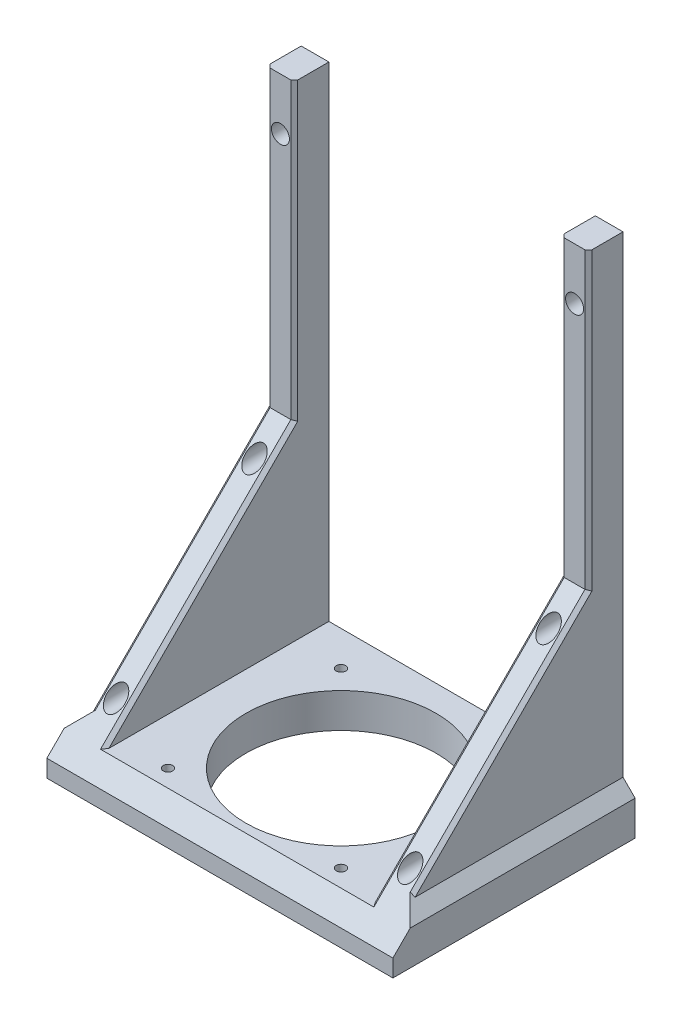
SolidWorks part; units mm, degrees
ref_plane "Front Plane" through (0, 0, 0) normal (0, 0, 1) x (1, 0, 0)
ref_plane "Top Plane" through (0, 0, 0) normal (0, 1, 0) x (1, 0, 0)
ref_plane "Right Plane" through (0, 0, 0) normal (1, 0, 0) x (0, 0, -1)
sketch "Sketch1" plane through (0, 0, 0) normal (0, 1, 0) x (1, 0, 0)
  line L1 (-70.1268, 59.4014) -> (29.8732, 59.4014)
  line L2 (-70.1268, 59.4014) -> (-70.1268, -10.5986)
  line L3 (-70.1268, -10.5986) -> (29.8732, -10.5986)
  line L4 (29.8732, 59.4014) -> (29.8732, -10.5986)
  line L5 (-70.1268, 59.4014) -> (29.8732, -10.5986) construction
  line L6 (-70.1268, -10.5986) -> (29.8732, 59.4014) construction
  line L15 (-40.8213, 9.9152) -> (14.7135, 48.7896) construction
  line L16 (-42.0419, 46.3165) -> (1.7884, 2.4863) construction
  line L17 (-45.1268, -0.5986) -> (4.8732, -0.5986)
  line L18 (-45.1268, -0.5986) -> (-45.1268, 49.4014)
  line L19 (-45.1268, 49.4014) -> (4.8732, 49.4014)
  line L20 (4.8732, -0.5986) -> (4.8732, 49.4014)
  line L21 (-45.1268, -0.5986) -> (4.8732, 49.4014) construction
  line L22 (-45.1268, 49.4014) -> (4.8732, -0.5986) construction
  circle A2 centre (-45.1268, 49.4014) radius 1.375
  circle A3 centre (4.8732, 49.4014) radius 1.375
  circle A4 centre (4.8732, -0.5986) radius 1.375
  circle A5 centre (-45.1268, -0.5986) radius 1.375
  circle A6 centre (-20.1268, 24.4014) radius 27.5
  point P0 (-20.1268, 24.4014)
  point P5 (-20.1268, 24.4014)
  point P8 (-20.1268, 24.4014)
  point P12 (-20.1268, 24.4014)
  dimension "D2" = 50
  dimension "D4" = 50
  dimension "D1" = 70
  dimension "D3" = 100
extrude "Boss-Extrude1" add sketch "Sketch1" against normal blind 10 contours L2 L3 L4 L1 | A2 | A3 | A6 | A4 | A5
sketch "Sketch3" plane through (0, 0, 0) normal (0, 1, 0) x (1, 0, 0)
  line L0 (-70.1268, 59.4014) -> (29.8732, 59.4014) construction
  line L1 (-55.1268, -10.5986) -> (14.8732, -10.5986)
  line L2 (-55.1268, -10.5986) -> (-55.1268, 59.4014)
  line L3 (-55.1268, 59.4014) -> (14.8732, 59.4014)
  line L4 (14.8732, -10.5986) -> (14.8732, 59.4014)
  line L5 (-55.1268, -10.5986) -> (14.8732, 59.4014) construction
  line L6 (-55.1268, 59.4014) -> (14.8732, -10.5986) construction
  line L7 (-70.1268, 59.4014) -> (-55.1268, 59.4014) construction
  line L8 (-20.1268, 59.4014) -> (-20.1268, -10.5986)
  line L9 (-66.6268, -10.5986) -> (-58.6268, -10.5986)
  line L10 (-66.6268, -10.5986) -> (-66.6268, 59.4014)
  line L11 (-66.6268, 59.4014) -> (-58.6268, 59.4014)
  line L12 (-58.6268, -10.5986) -> (-58.6268, 59.4014)
  line L13 (-66.6268, -10.5986) -> (-58.6268, 59.4014) construction
  line L14 (-66.6268, 59.4014) -> (-58.6268, -10.5986) construction
  line L15 (26.3732, 59.4014) -> (18.3732, 59.4014)
  line L16 (18.3732, -10.5986) -> (18.3732, 59.4014)
  line L17 (26.3732, -10.5986) -> (18.3732, -10.5986)
  line L18 (26.3732, -10.5986) -> (26.3732, 59.4014)
  point P0 (-20.1268, 24.4014)
  point P9 (-62.6268, 24.4014)
  line M15 (29.8732, 59.4014) -> (-70.1268, 59.4014)
  line M17 (-70.1268, -10.5986) -> (29.8732, -10.5986)
  dimension "D1" = 70
  dimension "D2" = 8
extrude "Boss-Extrude2" add sketch "Sketch3" along normal blind 55 contours L12 L10 M17 M15 | L18 L16 M17 M15 region at (-62.6268, 0, -24.4014) region at (22.3732, 0, -24.4014)
chamfer "Chamfer1" distance 60 angle 45 1 edges at (-62.6268, 55, 10.5986)
chamfer "Chamfer2" distance 3.5 angle 45 2 edges at (26.3732, 0, -26.9014) (-66.6268, 0, -26.9014)
sketch "Sketch5" plane through (0, 55, 0) normal (0, 1, 0) x (1, 0, 0)
  line L0 (18.3732, -5.5986) -> (18.3732, 59.4014) construction
  line L1 (-66.6268, 59.4014) -> (-58.6268, 59.4014)
  line L2 (-66.6268, 59.4014) -> (-66.6268, 49.4014)
  line L3 (-66.6268, 49.4014) -> (-58.6268, 49.4014)
  line L4 (-58.6268, 59.4014) -> (-58.6268, 49.4014)
  line L5 (26.3732, 59.4014) -> (18.3732, 59.4014)
  line L6 (26.3732, 59.4014) -> (26.3732, 49.4014)
  line L7 (26.3732, 49.4014) -> (18.3732, 49.4014)
  line L8 (18.3732, 59.4014) -> (18.3732, 49.4014)
  line L9 (18.3732, -5.5986) -> (18.3732, 49.4014) construction
extrude "Boss-Extrude3" add sketch "Sketch5" along normal blind 85
sketch "Sketch4" plane through (0, 0, -59.4014) normal (0, 0, -1) x (-1, 0, 0)
  line L0 (-22.3732, 7.5) -> (-22.3732, 47.5)
  line L1 (62.6268, 7.5) -> (62.6268, 47.5)
  line L2 (-22.3732, 140) -> (-22.3732, 125)
  line L3 (-26.3732, 140) -> (-18.3732, 140) construction
  line L4 (62.6268, 140) -> (62.6268, 125)
  line L5 (58.6268, 140) -> (66.6268, 140) construction
  circle A0 centre (-22.3732, 47.5) radius 1.375
  circle A1 centre (-22.3732, 7.5) radius 1.375
  circle A2 centre (62.6268, 47.5) radius 1.375
  circle A3 centre (62.6268, 7.5) radius 1.375
  circle A4 centre (-22.3732, 47.5) radius 2.6
  circle A5 centre (62.6268, 47.5) radius 2.6
  circle A6 centre (62.6268, 7.5) radius 2.6
  circle A7 centre (-22.3732, 7.5) radius 2.6
  circle A8 centre (-22.3732, 125) radius 1.375
  circle A9 centre (62.6268, 125) radius 1.375
  circle A10 centre (-22.3732, 125) radius 2.6
  circle A11 centre (62.6268, 125) radius 2.6
  point P3 (-22.3732, 27.5)
  point P6 (62.6268, 27.5)
extrude "Cut-Extrude1" cut sketch "Sketch4" against normal through all from offset 3.5 contours A4 | A5 | A6 | A7 | A10 | A11 offset against normal yes
extrude "Cut-Extrude2" cut sketch "Sketch4<3>" against normal through all contours A0 | A1 | A2 | A3 | A8 | A9
sketch "Sketch4<3>" plane through (0, 0, -59.4014) normal (0, 0, -1) x (-1, 0, 0) same geometry as "Sketch4"
chamfer "Chamfer3" distance 1 angle 45 8 edges at (26.3732, 29.25, -23.6514) (26.3732, 97.5, -49.4014) (18.3732, 27.5, -21.9014) (18.3732, 97.5, -49.4014) (-58.6268, 97.5, -49.4014) (-58.6268, 27.5, -21.9014) (-66.6268, 97.5, -49.4014) (-66.6268, 29.25, -23.6514)
